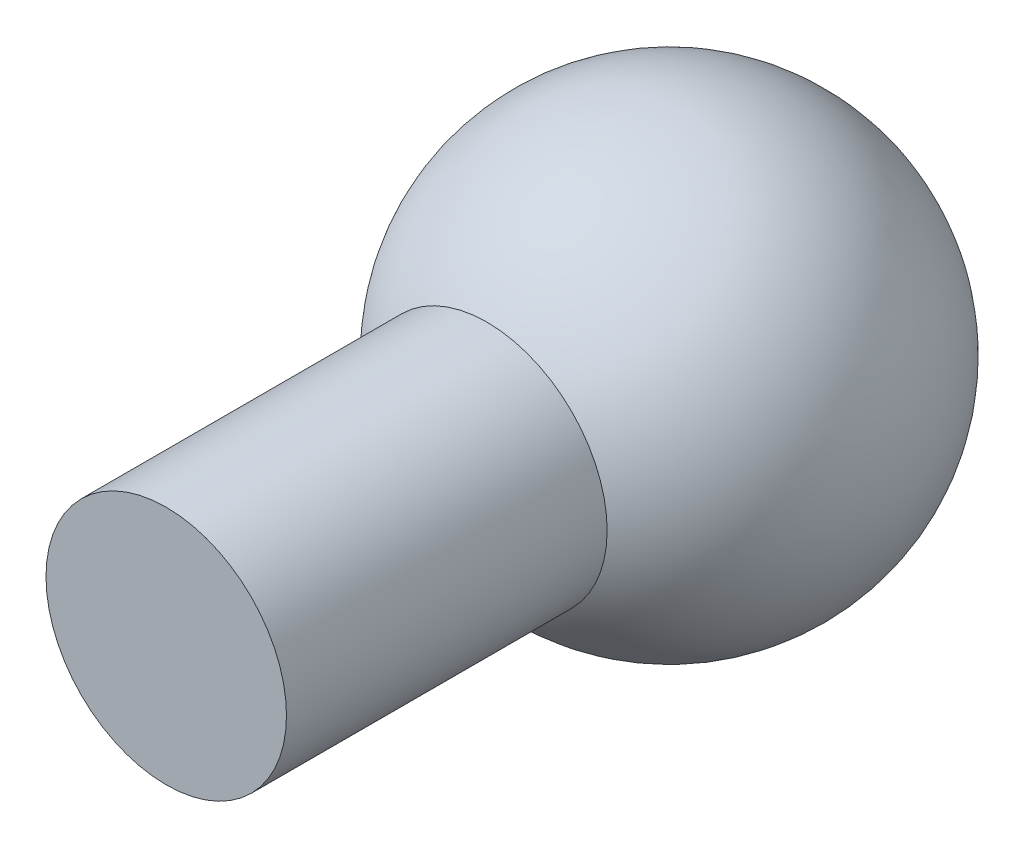
SolidWorks part; units mm, degrees
ref_plane "Front Plane" through (0, 0, 0) normal (0, 0, 1) x (1, 0, 0)
ref_plane "Top Plane" through (0, 0, 0) normal (0, 1, 0) x (1, 0, 0)
ref_plane "Right Plane" through (0, 0, 0) normal (1, 0, 0) x (0, 0, -1)
sketch "Sketch1" plane through (0, 0, 0) normal (0, 0, 1) x (1, 0, 0)
  circle A0 centre (0, 0) radius 1.5
  dimension "D1" = 3
extrude "Boss-Extrude1" add sketch "Sketch1" along normal blind 4
dome "Dome1" faces to dome 1 distance 5 reverse direction no elliptical dome no face at (1.5, 0, 0) parameters "D1"=5
